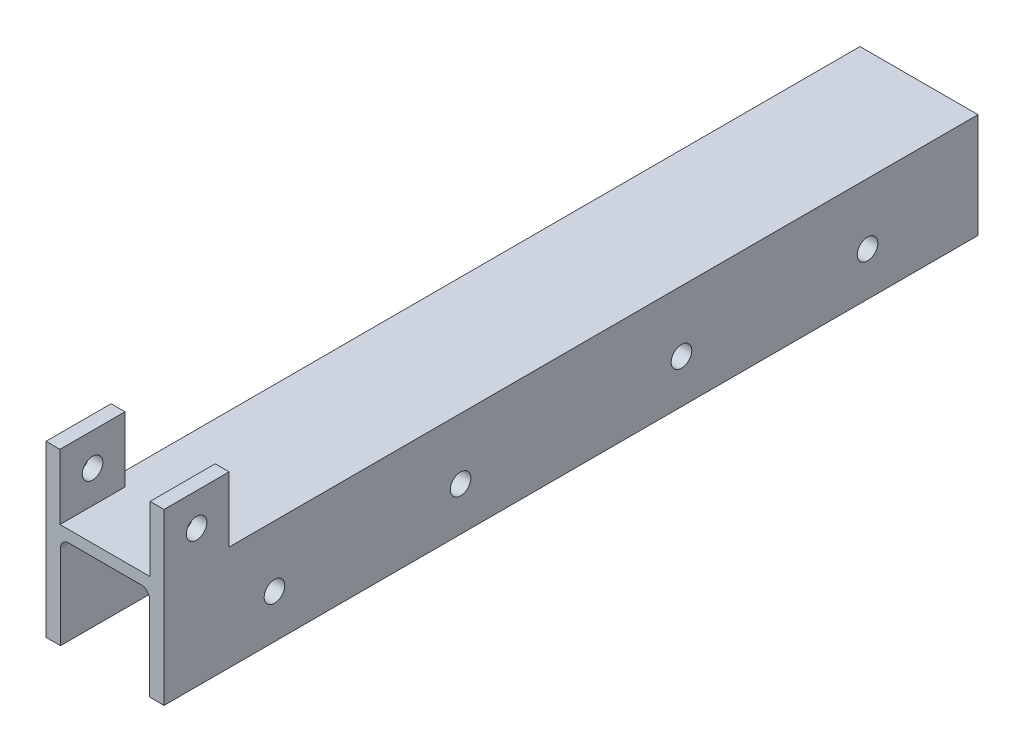
SolidWorks part; units mm, degrees
ref_plane "Front Plane" through (0, 0, 0) normal (0, 0, 1) x (1, 0, 0)
ref_plane "Top Plane" through (0, 0, 0) normal (0, 1, 0) x (1, 0, 0)
ref_plane "Right Plane" through (0, 0, 0) normal (1, 0, 0) x (0, 0, -1)
sketch "Sketch2" plane through (0, 0, 0) normal (0, 0, 1) x (1, 0, 0)
  line L0 (319.8414, 0) -> (-319.8414, 0) construction
  line L2 (0, 0) -> (0, 22.86)
  line L3 (0, 22.86) -> (25.781, 22.86)
  line L4 (25.781, 0) -> (25.781, 22.86)
  line L44 (22.606, 18.542) -> (22.606, 0)
  line L47 (3.175, 0) -> (3.175, 18.542)
  line L48 (4.953, 20.32) -> (20.828, 20.32)
  line L49 (0, 0) -> (3.175, 0)
  line L50 (22.606, 0) -> (25.781, 0)
  arc A0 (22.606, 18.542) -> (20.828, 20.32) centre (20.828, 18.542) ccw
  arc A1 (3.175, 18.542) -> (4.953, 20.32) centre (4.953, 18.542) cw
  point P15 (3.175, 20.32)
  point P16 (3.175, 20.32)
  dimension "D6" = 1.778
  dimension "D1" = 22.86
  dimension "D2" = 25.781
  dimension "D3" = 3.175
  dimension "D4" = 19.431
  dimension "D5" = 3.175
  dimension "D7" = 20.32
extrude "Boss-Extrude2" add sketch "Sketch2" against normal blind 177.8
sketch "Sketch19" plane through (0, 0, 0) normal (1, 0, 0) x (0, 0, -1)
  line L0 (0, 265.0009) -> (0, -265.0009) construction
  line L1 (319.8414, 0) -> (-319.8414, 0) construction
  line L2 (0, 20.32) -> (177.8, 20.32) construction
  line L3 (0, 0) -> (88.9, 0) construction
  line L4 (177.8, 0) -> (0, 0) construction
  line L5 (88.9, 0) -> (88.9, 22.86) construction
  line L6 (177.8, 22.86) -> (0, 22.86) construction
  line L7 (177.8, 0) -> (177.8, 22.86) construction
  circle A0 centre (24.13, 9.525) radius 2.2479
  circle A1 centre (64.77, 9.525) radius 2.2479
  circle A2 centre (113.03, 9.525) radius 2.2479
  circle A3 centre (153.67, 9.525) radius 2.2479
  dimension "D2" = 4.4958
  dimension "D5" = 4.4958
  dimension "D9" = 24.13
  dimension "D14" = 4.4958
  dimension "D1" = 24.13
  dimension "D3" = 9.525
  dimension "D4" = 40.64
  dimension "D6" = 9.525
  dimension "D7" = 24.13
  dimension "D8" = 88.9
  dimension "D10" = 40.64
  dimension "D11" = 24.13
  dimension "D12" = 2.54
  dimension "D13" = 20.32
extrude "Cut-Extrude3" cut sketch "Sketch19" along normal through all
sketch "Sketch21" plane through (0, 22.86, 0) normal (0, 1, 0) x (1, 0, 0)
  line L0 (12.8905, 0) -> (12.8905, 177.8) construction
  line L1 (0, 0) -> (25.781, 0) construction
  line L2 (0, 0) -> (3.048, 0)
  line L3 (0, 0) -> (0, 14.224)
  line L4 (0, 14.224) -> (3.048, 14.224)
  line L5 (3.048, 0) -> (3.048, 14.224)
  line L6 (25.781, 177.8) -> (0, 177.8) construction
  line L7 (0, 0) -> (6.096, 0) construction
  line L8 (6.096, 0) -> (6.096, 6.5548) construction
  line L10 (19.685, 0) -> (19.685, 6.5548) construction
  line L11 (25.781, 0) -> (22.733, 0)
  line L12 (25.781, 0) -> (25.781, 14.224)
  line L13 (25.781, 14.224) -> (22.733, 14.224)
  line L14 (22.733, 0) -> (22.733, 14.224)
  dimension "D1" = 6.096
  dimension "D2" = 6.096
  dimension "D3" = 14.224
  dimension "D4" = 13.589
  dimension "D5" = 3.048
  dimension "D6" = 3.048
  dimension "D7" = 14.224
extrude "Boss-Extrude4" add sketch "Sketch21" along normal blind 14.224
sketch "Sketch22" plane through (22.733, 0, 0) normal (-1, 0, 0) x (0, 0, 1)
  line L0 (0, 37.084) -> (-14.224, 37.084) construction
  line L1 (0, -265.0009) -> (0, 265.0009) construction
  line L2 (-14.224, 22.86) -> (0, 22.86) construction
  line L3 (-7.112, 22.86) -> (-7.112, 29.972) construction
  line L4 (-177.8, 0) -> (0, 0) construction
  circle A0 centre (-7.112, 29.972) radius 2.2479
  point P4 (-7.112, 37.084)
  dimension "D1" = 4.4958
  dimension "D2" = 7.112
  dimension "D3" = 7.112
  dimension "D4" = 14.224
  dimension "D5" = 7.112
  dimension "D6" = 29.972
extrude "Cut-Extrude4" cut sketch "Sketch22" against normal through all both and the other way through all
